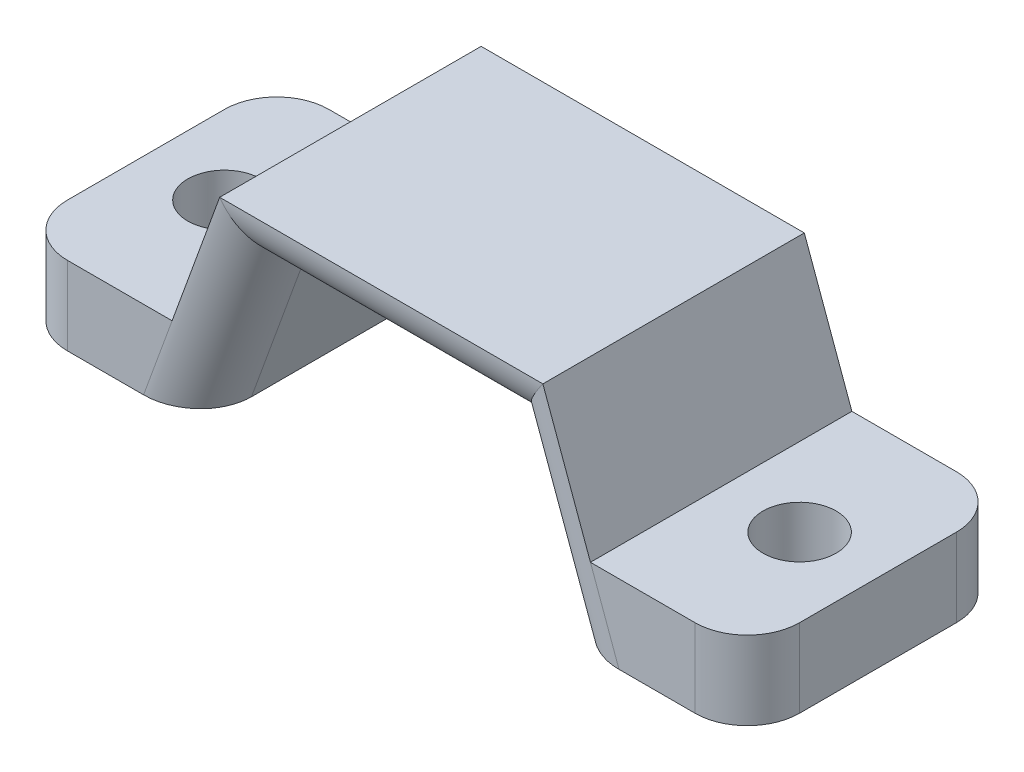
SolidWorks part; units mm, degrees
ref_plane "Front Plane" through (0, 0, 0) normal (0, 0, 1) x (1, 0, 0)
ref_plane "Top Plane" through (0, 0, 0) normal (0, 1, 0) x (1, 0, 0)
ref_plane "Right Plane" through (0, 0, 0) normal (1, 0, 0) x (0, 0, -1)
sketch "Sketch1" plane through (0, 0, 0) normal (0, 0, 1) x (1, 0, 0)
  line L0 (-14, 0) -> (-6.9636, 0)
  line L1 (-6.9636, 0) -> (-4.7797, 6)
  line L2 (-4.7797, 6) -> (4.7797, 6)
  line L3 (4.7797, 6) -> (6.9636, 0)
  line L4 (6.9636, 0) -> (14, 0)
  line L5 (14, 0) -> (14, 3)
  line L6 (14, 3) -> (8, 3)
  line L7 (8, 3) -> (6.1801, 8)
  line L8 (6.1801, 8) -> (-6.1801, 8)
  line L9 (-6.1801, 8) -> (-8, 3)
  line L10 (-8, 3) -> (-14, 3)
  line L11 (-14, 3) -> (-14, 0)
  point P2 (0, 8)
  point P15 (0, 6)
  dimension "D1" = 28
  dimension "D2" = 3
  dimension "D3" = 2
  dimension "D4" = 2
  dimension "D5" = 70
  dimension "D6" = 6
  dimension "D7" = 6
extrude "Boss-Extrude1" add sketch "Sketch1" along normal mid plane 10
sketch "Sketch2" plane through (0, 0, 0) normal (0, -1, 0) x (1, 0, 0)
  line L0 (-11, 0) -> (11, 0) construction
  circle A0 centre (-11, 0) radius 1.4
  circle A1 centre (11, 0) radius 1.4
  point P4 (0, 0)
  dimension "D2" = 2.8
  dimension "D1" = 22
extrude "Cut-Extrude1" cut sketch "Sketch2" against normal up to next
fillet "Fillet1" radius 2 6 edges at (-5.8716, 3, -5) (0, 6, -5) (5.8716, 3, -5) (5.8716, 3, 5) (-5.8716, 3, 5) (0, 6, 5)
fillet "Fillet2" radius 2 4 edges at (14, 1.5, 5) (14, 1.5, -5) (-14, 1.5, 5) (-14, 1.5, -5)
